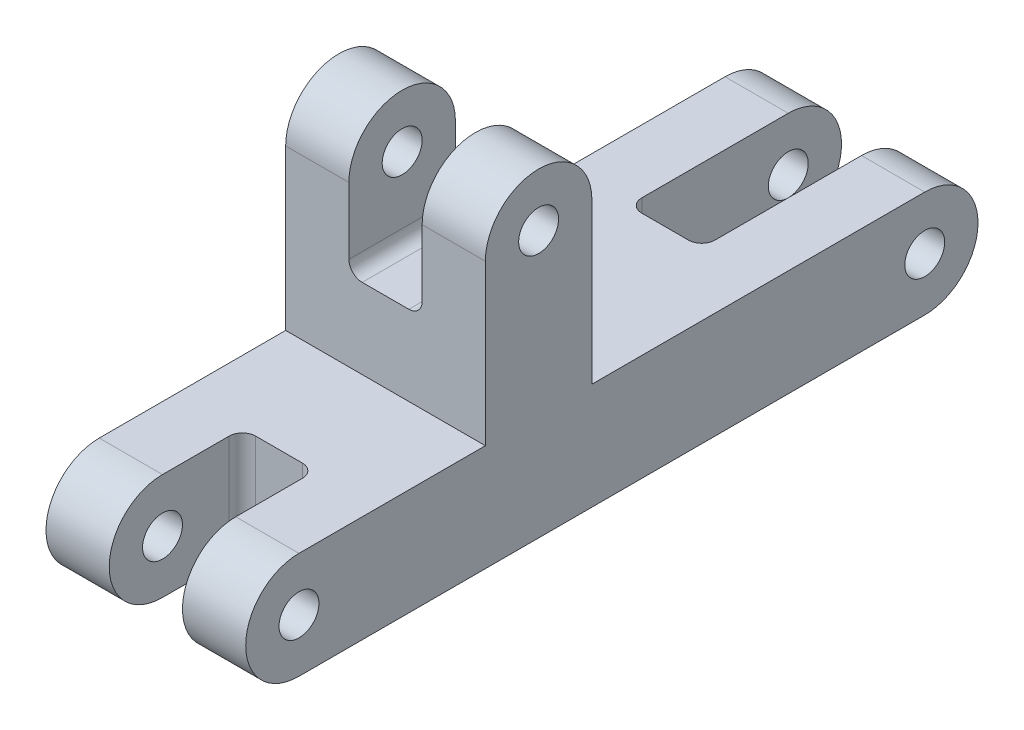
SolidWorks part; units mm, degrees
ref_plane "Alzado" through (0, 0, 0) normal (0, 0, 1) x (1, 0, 0)
ref_plane "Planta" through (0, 0, 0) normal (0, 1, 0) x (1, 0, 0)
ref_plane "Vista lateral" through (0, 0, 0) normal (1, 0, 0) x (0, 0, -1)
sketch "Croquis1" plane through (0, 0, 0) normal (1, 0, 0) x (0, 0, -1)
  line L0 (-12.5, 0) -> (12.5, 0) construction
  line L1 (-12.5, 4) -> (-20.5, 4) construction
  line L2 (-12.5, -4) -> (12.5, -4)
  line L3 (-12.5, 4) -> (12.5, 4)
  line L5 (-20.5, 4) -> (-20.5, 16)
  line L6 (-20.5, 16) -> (-12.5, 16) construction
  line L7 (-12.5, 4) -> (-12.5, 16)
  line L8 (-20.5, 4) -> (-34.5, 4)
  line L9 (-12.5, -4) -> (-34.5, -4)
  line L10 (-34.5, 4) -> (-34.5, -4) construction
  arc A0 (-12.5, 4) -> (-12.5, -4) centre (-12.5, 0) ccw construction
  arc A1 (12.5, -4) -> (12.5, 4) centre (12.5, 0) ccw
  circle A2 centre (12.5, 0) radius 1.5
  arc A3 (-12.5, 16) -> (-20.5, 16) centre (-16.5, 16) ccw
  circle A4 centre (-16.5, 16) radius 1.5
  circle A5 centre (-12.5, 0) radius 1.5 construction
  arc A6 (-34.5, 4) -> (-34.5, -4) centre (-34.5, 0) ccw
  circle A7 centre (-34.5, 0) radius 1.5
  point P3 (0, 0)
  dimension "D2" = 4
  dimension "D3" = 3
  dimension "D4" = 4
  dimension "D7" = 14
  dimension "D1" = 25
  dimension "D6" = 12
extrude "Saliente-Extruir1" add sketch "Croquis1" along normal mid plane 15
sketch "Croquis2" plane through (0, 0, 0) normal (1, 0, 0) x (0, 0, -1)
  line L0 (-20.5, 16) -> (-20.5, 4) construction
  line L1 (-20.5, 10) -> (-12.5, 10)
  line L2 (-20.5, 10) -> (-20.5, 20)
  line L3 (-20.5, 20) -> (-12.5, 20)
  line L4 (-12.5, 10) -> (-12.5, 20)
  line L5 (-12.5, 4) -> (-12.5, 16) construction
  line L11 (-34.5, -4) -> (12.5, -4) construction
  line L12 (12.5, 4) -> (-12.5, 4) construction
  line L13 (0.5, 4) -> (16.5, 4)
  line L14 (0.5, 4) -> (0.5, -4)
  line L15 (0.5, -4) -> (16.5, -4)
  line L16 (16.5, 4) -> (16.5, -4)
  line L18 (-28.5, 4) -> (-38.5, 4)
  line L19 (-28.5, 4) -> (-28.5, -4)
  line L20 (-28.5, -4) -> (-38.5, -4)
  line L21 (-38.5, 4) -> (-38.5, -4)
  line L22 (-34.5, -4) -> (12.5, -4) construction
  line L23 (-20.5, 4) -> (-34.5, 4) construction
  arc A0 (-12.5, 16) -> (-20.5, 16) centre (-16.5, 16) ccw construction
  arc A2 (12.5, -4) -> (12.5, 4) centre (12.5, 0) ccw construction
  arc A5 (-34.5, 4) -> (-34.5, -4) centre (-34.5, 0) ccw construction
  dimension "D5" = 10
  dimension "D1" = 10
  dimension "D3" = 16
extrude "Cortar-Extruir1" cut sketch "Croquis2" against normal mid plane 5.5
fillet "Redondeo1" radius 1 6 edges at (2.75, 0, 28.5) (-2.75, 0, 28.5) (2.75, 0, -0.5) (-2.75, 0, -0.5) (2.75, 10, 16.5) (-2.75, 10, 16.5)
